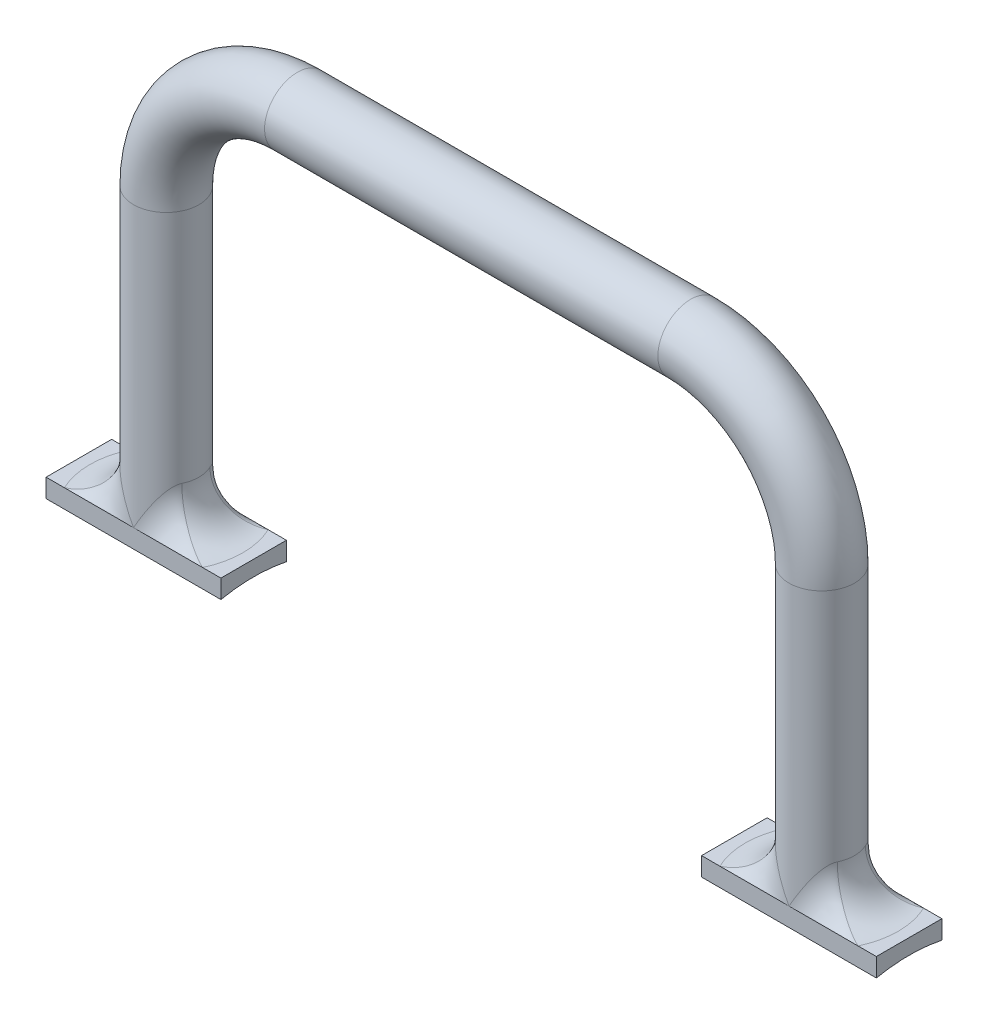
SolidWorks part; units mm, degrees
material "6061-T6 (SS)"
ref_plane "Front Plane" through (0, 0, 0) normal (0, 0, 1) x (1, 0, 0)
ref_plane "Top Plane" through (0, 0, 0) normal (0, 1, 0) x (1, 0, 0)
ref_plane "Right Plane" through (0, 0, 0) normal (1, 0, 0) x (0, 0, -1)
sketch "Sketch1" plane through (0, 0, 0) normal (0, 0, 1) x (1, 0, 0)
  line L1 (-75, -50) -> (75, -50)
  line L2 (-75, -50) -> (-75, 50)
  line L3 (-75, 50) -> (75, 50)
  line L4 (75, -50) -> (75, 50)
  line L5 (-75, -50) -> (75, 50) construction
  line L6 (-75, 50) -> (75, -50) construction
  point P0 (0, 0)
  dimension "D1" = 150
  dimension "D2" = 100
extrude "Boss-Extrude1" [suppressed] add sketch "Sketch1" along normal blind 20
sketch "Sketch2" [suppressed] plane through (0, 0, 20) normal (0, 0, 1) x (1, 0, 0)
  line L0 (-66.1943, -50) -> (-59.0828, 39.6734)
  line L1 (-75, -50) -> (75, -50) construction
  line L2 (-59.0828, 39.6734) -> (48.1668, 39.6734)
  line L3 (48.1668, 39.6734) -> (65.3374, -50)
  line L4 (-66.1943, -50) -> (65.3374, -50)
extrude "Cut-Extrude2" [suppressed] cut sketch "Sketch2" against normal through all and the other way through all
sketch "Sketch4" plane through (0, 0, 0) normal (0, 0, 1) x (1, 0, 0)
  line L0 (-93.3072, 70) -> (-93.3072, 0)
  line L1 (-63.3072, 100) -> (26.6928, 100)
  line L3 (56.6928, 70) -> (56.6928, 0)
  line L4 (-93.3072, 100) -> (56.6928, 0) construction
  line L5 (-93.3072, 0) -> (56.6928, 100) construction
  arc A0 (56.6928, 70) -> (26.6928, 100) centre (26.6928, 70) ccw
  arc A1 (-63.3072, 100) -> (-93.3072, 70) centre (-63.3072, 70) ccw
  point P1 (-18.3072, 50)
  dimension "D3" = 30
  dimension "D1" = 100
  dimension "D2" = 150
sketch "Sketch5" plane through (0, 0, 0) normal (0, 1, 0) x (1, 0, 0)
  circle A0 centre (-93.3072, 0) radius 7.5
  circle A1 centre (-93.3072, 0) radius 4.1695
  dimension "D1" = 15
sweep "Sweep1" add profiles "Sketch5" path "Sketch4"
sketch "Sketch6" plane through (0, 0, 0) normal (0, 1, 0) x (1, 0, 0)
  line L0 (26.6928, -7.5) -> (56.6928, -7.5) construction
  line L1 (-73.3072, 7.5) -> (-113.3072, 7.5)
  line L2 (-73.3072, 7.5) -> (-73.3072, -7.5)
  line L3 (-73.3072, -7.5) -> (-113.3072, -7.5)
  line L4 (-113.3072, 7.5) -> (-113.3072, -7.5)
  line L5 (-73.3072, 7.5) -> (-113.3072, -7.5) construction
  line L6 (-73.3072, -7.5) -> (-113.3072, 7.5) construction
  line L7 (76.6928, 7.5) -> (36.6928, 7.5)
  line L8 (76.6928, 7.5) -> (76.6928, -7.5)
  line L9 (76.6928, -7.5) -> (36.6928, -7.5)
  line L10 (36.6928, 7.5) -> (36.6928, -7.5)
  line L11 (76.6928, 7.5) -> (36.6928, -7.5) construction
  line L12 (76.6928, -7.5) -> (36.6928, 7.5) construction
  point P0 (-93.3072, 0)
  point P6 (56.6928, 0)
  dimension "D1" = 40
  dimension "D2" = 40
extrude "Boss-Extrude2" add sketch "Sketch6" along normal blind 6
fillet "Fillet1" radius 10 4 edges at (-85.8072, 6, 0) (-100.8072, 6, 0) (64.1928, 6, 0) (49.1928, 6, 0)
sketch "Sketch7" plane through (76.6928, 0, 0) normal (1, 0, 0) x (0, 0, -1)
  line L0 (-7.5, 0) -> (7.5, 0) construction
  circle A0 centre (0, -35) radius 37.5
  dimension "D1" = 75
  dimension "D2" = 35
extrude "Cut-Extrude3" cut sketch "Sketch7" against normal through all
